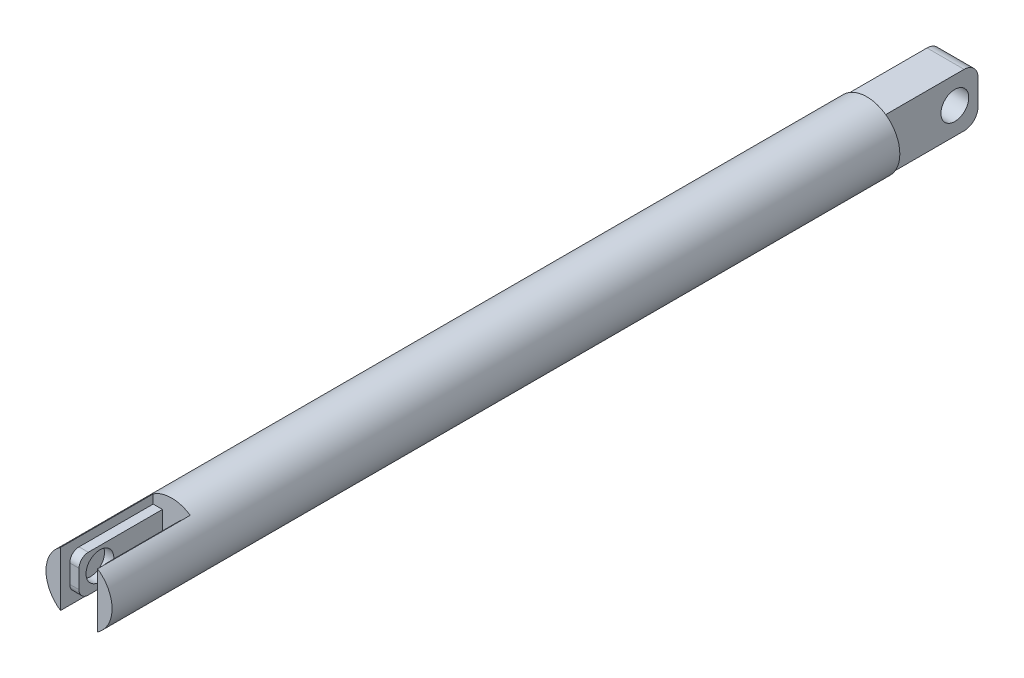
SolidWorks part; units mm, degrees
ref_plane "前视基准面" through (0, 0, 0) normal (0, 0, 1) x (1, 0, 0)
ref_plane "上视基准面" through (0, 0, 0) normal (0, 1, 0) x (1, 0, 0)
ref_plane "右视基准面" through (0, 0, 0) normal (1, 0, 0) x (0, 0, -1)
other "Configuration Table"
sketch "草图1" plane through (0, 0, 0) normal (0, 0, 1) x (1, 0, 0)
  line L1 (-2, -4) -> (2, -4)
  line L2 (-2, -4) -> (-2, 4)
  line L3 (-2, 4) -> (2, 4)
  line L4 (2, -4) -> (2, 4)
  line L5 (0, 4) -> (0, -4) construction
  line L6 (-2, 0) -> (2, 0) construction
  line L11 (2, 4) -> (4, 4)
  line L12 (2, 4) -> (2, -4)
  line L13 (2, -4) -> (4, -4)
  line L14 (4, 4) -> (4, -4)
  line L27 (-2, 4) -> (-4, 4)
  line L28 (-2, 4) -> (-2, -4)
  line L29 (-2, -4) -> (-4, -4)
  line L30 (-4, 4) -> (-4, -4)
  circle A0 centre (0, 0) radius 7.1295
  dimension "D1" = 4
  dimension "D2" = 8
  dimension "D3" = 2
  dimension "D4" = 2
extrude "凸台-拉伸2" add sketch "草图1" along normal blind 8 contours L27 L30 L29 L2 | L14 L11 L4 L13 region at (-3, 0, 0) region at (3, 0, 0)
extrude "凸台-拉伸3" add sketch "草图1<3>" against normal blind 150 contours A0
sketch "草图1<3>" plane through (0, 0, 0) normal (0, 0, 1) x (1, 0, 0) same geometry as "草图1"
sketch "草图2" plane through (0, 0, 8) normal (0, 0, 1) x (1, 0, 0)
  line L1 (2, 4) -> (4, 4)
  line L2 (2, 4) -> (2, -4)
  line L3 (2, -4) -> (4, -4)
  line L4 (4, 4) -> (4, -4)
  line L9 (-4, 4) -> (-2, 4)
  line L10 (-4, 4) -> (-4, -4)
  line L11 (-4, -4) -> (-2, -4)
  line L12 (-2, 4) -> (-2, -4)
extrude "凸台-拉伸4" add sketch "草图2" along normal blind 10
fillet "圆角2" radius 2 1 edges at (-3, -4, 18) type face fillet first side face at (-3, 0, 18) second side face at (-3, -4, 9)
fillet "圆角3" radius 2 1 edges at (3, -4, 18) type face fillet first side face at (3, 0, 18) second side face at (3, -4, 9)
fillet "圆角4" radius 2 1 edges at (-3, 4, 18) type face fillet first side face at (-3, 4, 9) second side face at (-3, 1, 18)
fillet "圆角5" radius 2 1 edges at (3, 4, 18) type face fillet first side face at (3, 4, 9) second side face at (3, 1, 18)
sketch "草图3" plane through (-4, 0, 0) normal (-1, 0, 0) x (0, 0, 1)
  line L0 (18, 0.2003) -> (13.5, 0.2003)
  line L1 (18, 2) -> (18, -2) construction
  circle A0 centre (13.5, 0.2003) radius 3
extrude "切除-拉伸1" cut sketch "草图3" against normal blind 10 contours A0 region at (-4, 0.2003, 10.5849)
sketch "草图4" plane through (0, 0, 0) normal (0, 0, 1) x (1, 0, 0)
  line L0 (-4, 0) -> (-4, 5.9017)
  line L1 (-4, 4) -> (-4, -4) construction
  line L2 (-4, 0) -> (-4, -5.9017)
  line L3 (4, 0) -> (4, 5.9017)
  line L4 (4, -2) -> (4, 2) construction
  line L5 (4, 0) -> (4, -5.9017)
  circle A0 centre (0, 0) radius 7.1295
  line M1 (4, 4) -> (4, -4)
  circle M5 centre (0, 0) radius 7.1295
  line M9 (-4, -4) -> (-4, 4)
extrude "凸台-拉伸5" add sketch "草图4" along normal blind 20 contours L2 L0 M9 M5 | L5 L3 M1 M5 region at (-5.2788, 0, 0) region at (5.2788, 0, 0)
sketch "草图5" plane through (0, 0, -150) normal (0, 0, -1) x (-1, 0, 0)
  line L1 (-4, -5.75) -> (4, -5.75)
  line L2 (-4, -5.75) -> (-4, 5.75)
  line L3 (-4, 5.75) -> (4, 5.75)
  line L4 (4, -5.75) -> (4, 5.75)
  line L5 (0, 5.75) -> (0, -5.75) construction
  line L6 (-4, 0) -> (4, 0) construction
  circle A0 centre (0, 0) radius 7.1295
  dimension "D1" = 8
extrude "凸台-拉伸6" add sketch "草图5" along normal blind 20 contours L2 L1 L4 L3
fillet "圆角6" radius 3 1 edges at (0, -5.75, -170) type face fillet first side face at (0, 0, -170) second side face at (0, -5.75, -160)
fillet "圆角7" radius 3 1 edges at (0, 5.75, -170) type face fillet first side face at (0, 5.75, -160) second side face at (0, 1.5, -170)
sketch "草图6" plane through (4, 0, 0) normal (1, 0, 0) x (0, 0, -1)
  line L0 (170, 0) -> (165, 0) construction
  line L1 (170, -2.75) -> (170, 2.75) construction
  circle A0 centre (165, 0) radius 3
extrude "切除-拉伸2" cut sketch "草图6" against normal blind 20
